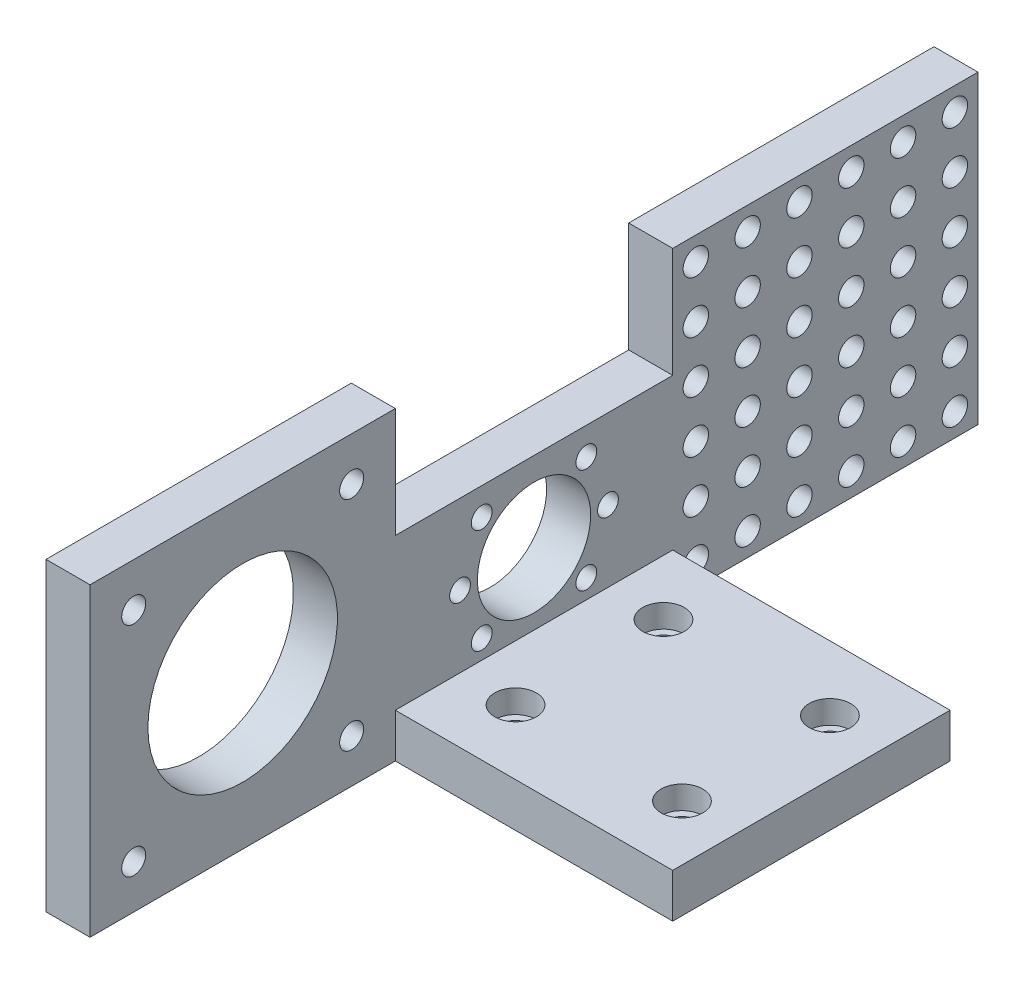
SolidWorks part; units mm, degrees
ref_plane "Front Plane" through (0, 0, 0) normal (0, 0, 1) x (1, 0, 0)
ref_plane "Top Plane" through (0, 0, 0) normal (0, 1, 0) x (1, 0, 0)
ref_plane "Right Plane" through (0, 0, 0) normal (1, 0, 0) x (0, 0, -1)
sketch "Sketch1" plane through (0, 0, 0) normal (0, 1, 0) x (1, 0, 0)
  line L0 (30, 60) -> (30, 0) construction
  line L1 (0, 0) -> (60, 0)
  line L2 (0, 0) -> (0, 60)
  line L3 (0, 60) -> (60, 60)
  line L4 (60, 0) -> (60, 60)
  line L5 (12, 46) -> (48, 46) construction
  line L6 (12, 46) -> (12, 14) construction
  line L7 (12, 14) -> (48, 14) construction
  line L8 (48, 46) -> (48, 14) construction
  line L9 (0, 30) -> (60, 30) construction
  circle A0 centre (12, 14) radius 2.95
  circle A1 centre (12, 46) radius 2.95
  circle A2 centre (48, 46) radius 2.95
  circle A3 centre (48, 14) radius 2.95
  dimension "D3" = 5.9
  dimension "D1" = 36
  dimension "D2" = 32
  dimension "D4" = 60
  dimension "D5" = 60
extrude "Boss-Extrude1" add sketch "Sketch1" along normal blind 9.525
sketch "Sketch2" plane through (0, 9.525, 0) normal (0, 1, 0) x (1, 0, 0)
  circle A0 centre (12, 14) radius 4.5
  circle A1 centre (12, 46) radius 4.5
  circle A2 centre (48, 46) radius 4.5
  circle A3 centre (48, 14) radius 4.5
  dimension "D1" = 9
extrude "Cut-Extrude1" cut sketch "Sketch2" against normal blind 5
sketch "Sketch3" plane through (0, 0, 0) normal (-1, 0, 0) x (0, 0, 1)
  line L0 (-60, 9.525) -> (0, 9.525) construction
  line L1 (-60, 0) -> (0, 0)
  line L2 (-60, 0) -> (-60, 42.25)
  line L3 (-60, 42.25) -> (0, 42.25)
  line L4 (0, 0) -> (0, 42.25)
  line L6 (0, 9.525) -> (0, 0) construction
  line L7 (-30, 44.025) -> (-30, 0) construction
  line L8 (-30, 25) -> (0, 25) construction
  line L9 (-30, 25) -> (-18.6863, 36.3137) construction
  circle A0 centre (-30, 25) radius 12.25
  circle A1 centre (-30, 25) radius 16 construction
  circle A2 centre (-18.6863, 36.3137) radius 2.25
  circle A3 centre (-14, 25) radius 2.25
  circle A4 centre (-18.6863, 13.6863) radius 2.25
  circle A5 centre (-41.3137, 13.6863) radius 2.25
  circle A6 centre (-46, 25) radius 2.25
  circle A7 centre (-41.3137, 36.3137) radius 2.25
  point P14 (-30, 42.25)
  dimension "D1" = 24.5
  dimension "D2" = 15.475
  dimension "D3" = 5
  dimension "D4" = 32
  dimension "D6" = 4.5
  dimension "D5" = 45
  dimension "D7" = 3
extrude "Boss-Extrude2" add sketch "Sketch3" along normal blind 9.525
sketch "Sketch4" plane through (-9.525, 0, 0) normal (-1, 0, 0) x (0, 0, 1)
  line L0 (33.02, 72.7999) -> (33.02, 6.7599) construction
  line L1 (0, 0) -> (66.04, 0)
  line L2 (0, 0) -> (0, 66.04)
  line L3 (0, 66.04) -> (66.04, 66.04)
  line L4 (66.04, 0) -> (66.04, 66.04)
  line L5 (9.45, 56.59) -> (56.59, 56.59) construction
  line L6 (9.45, 56.59) -> (9.45, 9.45) construction
  line L7 (9.45, 9.45) -> (56.59, 9.45) construction
  line L8 (56.59, 56.59) -> (56.59, 9.45) construction
  line L9 (46.2537, 33.02) -> (-19.7863, 33.02) construction
  line L11 (0, 0) -> (0, 42.25) construction
  line L14 (-60, 0) -> (0, 0) construction
  line L15 (-30, 98.1688) -> (-30, 122.9789) construction
  line L16 (-60, 66.04) -> (-126.04, 66.04)
  line L17 (-126.04, 0) -> (-126.04, 66.04)
  line L18 (-60, 0) -> (-126.04, 0)
  line L19 (-60, 0) -> (-60, 66.04)
  circle A0 centre (56.59, 56.59) radius 2.6
  circle A1 centre (9.45, 56.59) radius 2.6
  circle A2 centre (9.45, 9.45) radius 2.6
  circle A3 centre (56.59, 9.45) radius 2.6
  circle A4 centre (33.02, 33.02) radius 20.5
  circle A6 centre (-30, 25) radius 12.25 construction
  circle A7 centre (-121.04, 61.04) radius 2.75
  circle A8 centre (-109.832, 61.04) radius 2.75
  circle A9 centre (-98.624, 61.04) radius 2.75
  circle A10 centre (-87.416, 61.04) radius 2.75
  circle A11 centre (-76.208, 61.04) radius 2.75
  circle A12 centre (-65, 61.04) radius 2.75
  circle A13 centre (-109.832, 49.832) radius 2.75
  circle A14 centre (-98.624, 49.832) radius 2.75
  circle A15 centre (-87.416, 49.832) radius 2.75
  circle A16 centre (-76.208, 49.832) radius 2.75
  circle A17 centre (-65, 49.832) radius 2.75
  circle A18 centre (-109.832, 38.624) radius 2.75
  circle A19 centre (-98.624, 38.624) radius 2.75
  circle A20 centre (-87.416, 38.624) radius 2.75
  circle A21 centre (-76.208, 38.624) radius 2.75
  circle A22 centre (-65, 38.624) radius 2.75
  circle A23 centre (-109.832, 27.416) radius 2.75
  circle A24 centre (-98.624, 27.416) radius 2.75
  circle A25 centre (-87.416, 27.416) radius 2.75
  circle A26 centre (-76.208, 27.416) radius 2.75
  circle A27 centre (-65, 27.416) radius 2.75
  circle A28 centre (-109.832, 16.208) radius 2.75
  circle A29 centre (-98.624, 16.208) radius 2.75
  circle A30 centre (-87.416, 16.208) radius 2.75
  circle A31 centre (-76.208, 16.208) radius 2.75
  circle A32 centre (-65, 16.208) radius 2.75
  circle A33 centre (-109.832, 5) radius 2.75
  circle A34 centre (-98.624, 5) radius 2.75
  circle A35 centre (-87.416, 5) radius 2.75
  circle A36 centre (-76.208, 5) radius 2.75
  circle A37 centre (-65, 5) radius 2.75
  circle A38 centre (-121.04, 49.832) radius 2.75
  circle A39 centre (-121.04, 38.624) radius 2.75
  circle A40 centre (-121.04, 27.416) radius 2.75
  circle A41 centre (-121.04, 16.208) radius 2.75
  circle A42 centre (-121.04, 5) radius 2.75
  point P17 (66.04, 33.02)
  point P18 (33.02, 66.04)
  point P26 (0, 0)
  point P28 (-30, 25)
  dimension "D3" = 5.2
  dimension "D5" = 41
  dimension "D6" = 5.5
  dimension "D1" = 66.04
  dimension "D2" = 66.04
  dimension "D4" = 47.14
  dimension "D7" = 5
  dimension "D8" = 5
  dimension "D11" = 5
  dimension "D12" = 5
  dimension "D9" = 6
  dimension "D10" = 6
extrude "Boss-Extrude3" add sketch "Sketch4" against normal blind 9.525
